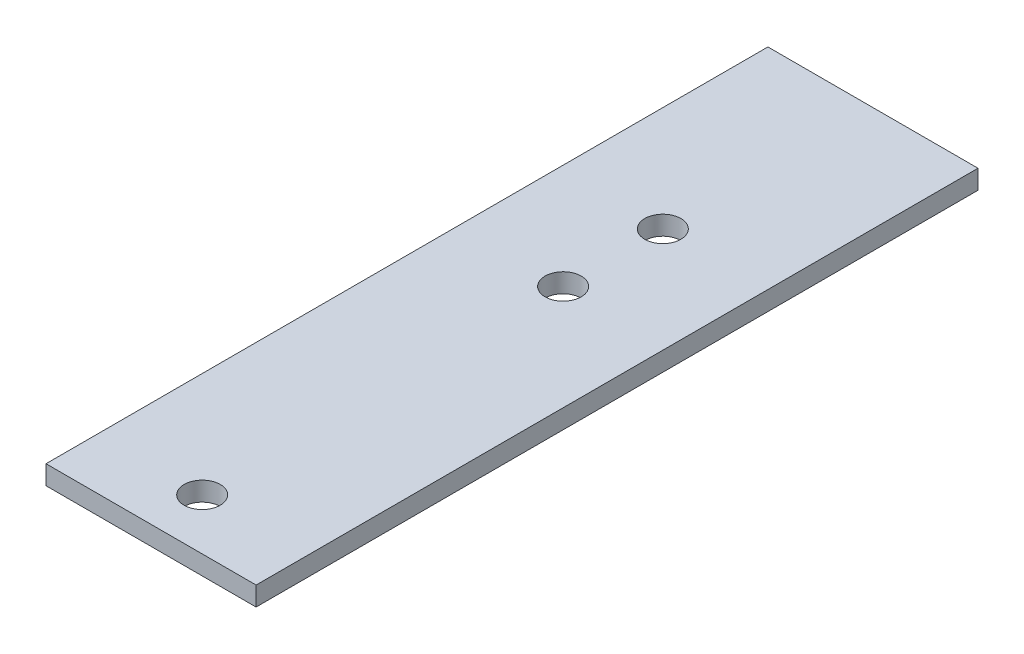
SolidWorks part; units mm, degrees
ref_plane "Front Plane" through (0, 0, 0) normal (0, 0, 1) x (1, 0, 0)
ref_plane "Top Plane" through (0, 0, 0) normal (0, 1, 0) x (1, 0, 0)
ref_plane "Right Plane" through (0, 0, 0) normal (1, 0, 0) x (0, 0, -1)
ref_plane "Plane1" through (0, -34.925, 0) normal (0, -1, 0) x (1, 0, 0)
sketch "Sketch1" plane through (0, -34.925, 0) normal (0, -1, 0) x (1, 0, 0)
  line L0 (-3.175, -115) -> (34.925, -115)
  line L1 (34.925, -115) -> (34.925, 5)
  line L2 (34.925, 5) -> (-3.175, 5)
  line L3 (-3.175, 5) -> (-3.175, -115)
extrude "Boss-Extrude1" add sketch "Sketch1" against normal blind 38.1
sketch "Sketch2" plane through (0, 0, -115) normal (0, 0, -1) x (-1, 0, 0)
  line L0 (-34.925, -34.925) -> (0, -34.925)
  line L1 (0, -34.925) -> (0, 0)
  line L2 (0, 0) -> (-34.925, 0)
  line L3 (-34.925, 0) -> (-34.925, -34.925)
extrude "Cut-Extrude1" cut sketch "Sketch2" against normal through all
sketch "Sketch18" plane through (0, 0, 5) normal (0, 0, 1) x (1, 0, 0)
  line L1 (-3.175, 3.175) -> (0, 3.175)
  line L2 (-3.175, 3.175) -> (-3.175, 0)
  line L3 (-3.175, 0) -> (0, 0)
  line L4 (0, 3.175) -> (0, 0)
extrude "Cut-Extrude3" cut sketch "Sketch18" against normal through all
sketch "Sketch19" plane through (0, 0, 0) normal (0, -1, 0) x (1, 0, 0)
  line L0 (17.4625, 5) -> (17.4625, -115) construction
  line L1 (0, 5) -> (34.925, 5) construction
  line L2 (0, -115) -> (34.925, -115) construction
  circle A0 centre (17.4625, -80.07) radius 3
  circle A1 centre (17.4625, -63.5) radius 3
  circle A2 centre (17.4625, -3.5) radius 3
  dimension "D1" = 6
  dimension "D2" = 6
  dimension "D3" = 6
  dimension "D4" = 34.93
  dimension "D6" = 111.5
  dimension "D5" = 51.5
extrude "Cut-Extrude4" cut sketch "Sketch19" against normal through all
